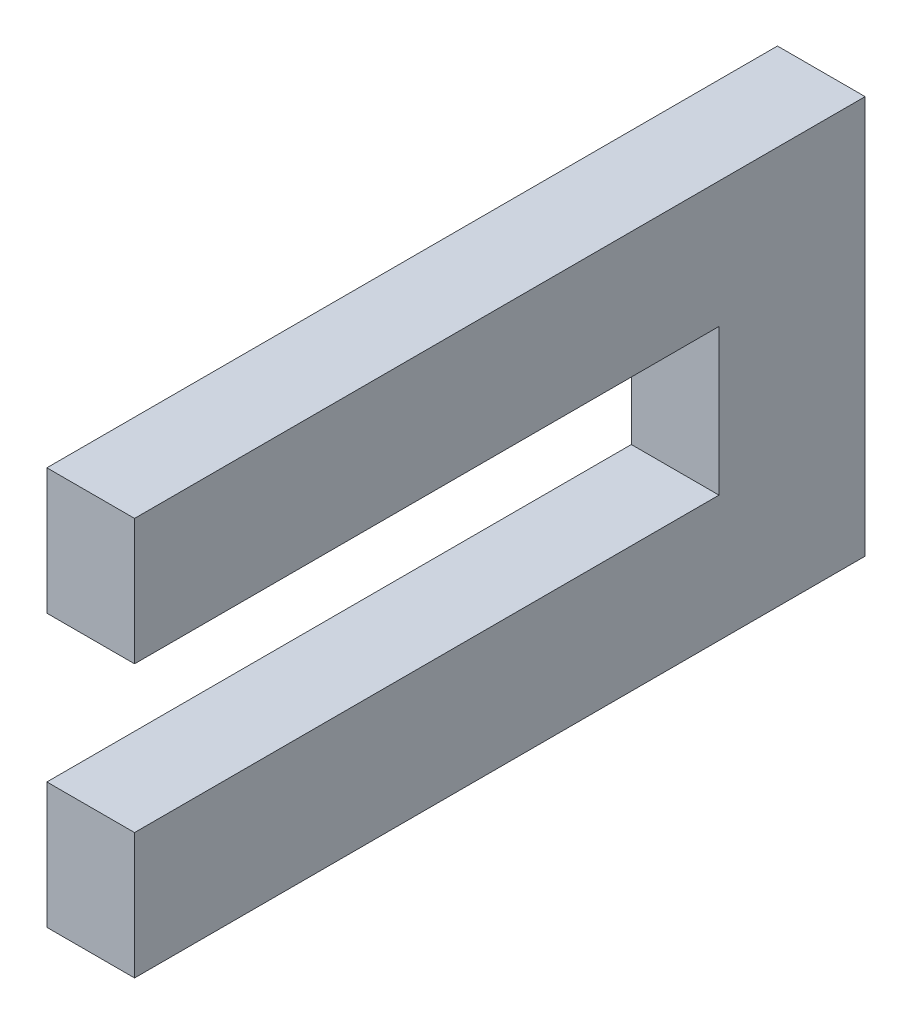
SolidWorks part; units mm, degrees
ref_plane "Front Plane" through (0, 0, 0) normal (0, 0, 1) x (1, 0, 0)
ref_plane "Top Plane" through (0, 0, 0) normal (0, 1, 0) x (1, 0, 0)
ref_plane "Right Plane" through (0, 0, 0) normal (1, 0, 0) x (0, 0, -1)
sketch "Sketch2" plane through (0, 0, 0) normal (1, 0, 0) x (0, 0, -1)
  line L0 (-20.4527, -4.3885) -> (4.5473, -4.3885)
  line L1 (4.5473, -4.3885) -> (4.5473, -18.0092)
  line L2 (4.5473, -18.0092) -> (-20.4527, -18.0092)
  line L3 (-20.4527, -18.0092) -> (-20.4527, -13.6989)
  line L4 (-20.4527, -13.6989) -> (-0.4527, -13.6989)
  line L5 (-0.4527, -13.6989) -> (-0.4527, -8.6989)
  line L6 (-0.4527, -8.6989) -> (-20.4527, -8.6989)
  line L7 (-20.4527, -8.6989) -> (-20.4527, -4.3885)
  dimension "D1" = 5
  dimension "D2" = 20
  dimension "D3" = 25
extrude "Boss-Extrude1" add sketch "Sketch2" along normal blind 3
